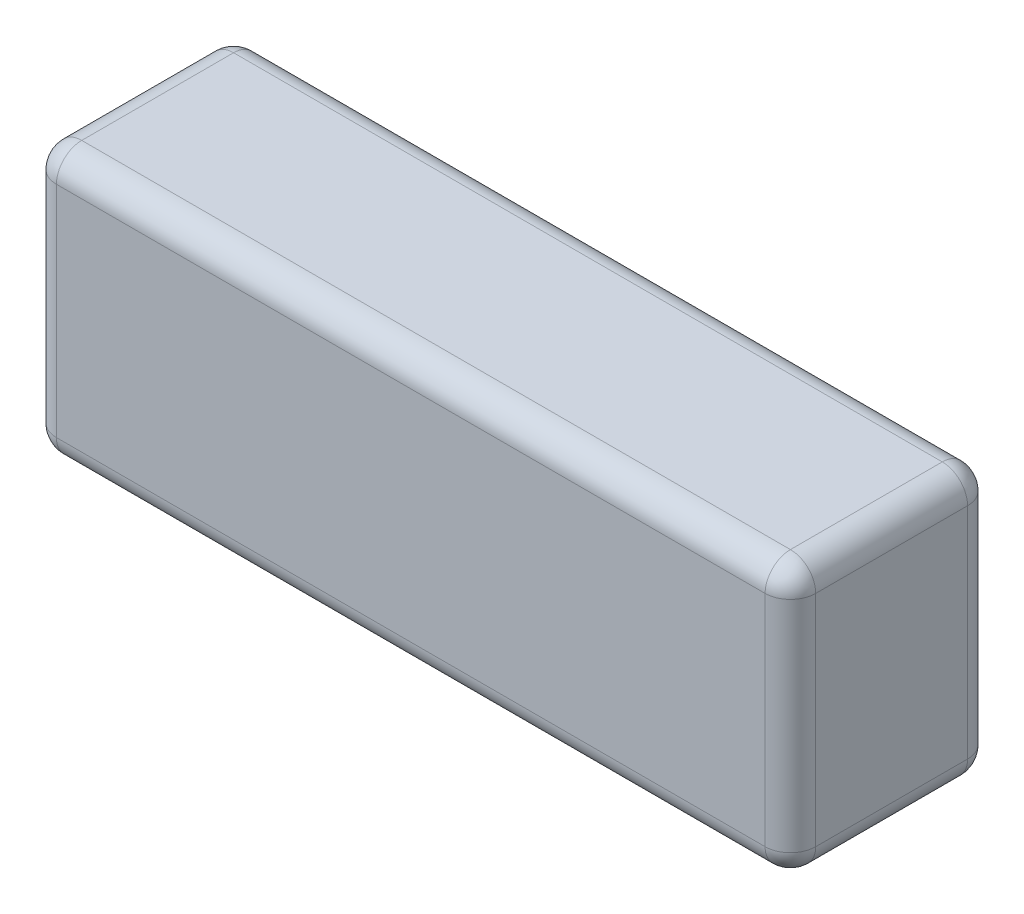
SolidWorks part; units mm, degrees
ref_plane "Plano frontal" through (0, 0, 0) normal (0, 0, 1) x (1, 0, 0)
ref_plane "Plano superior" through (0, 0, 0) normal (0, 1, 0) x (1, 0, 0)
ref_plane "Plano direito" through (0, 0, 0) normal (1, 0, 0) x (0, 0, -1)
sketch "Esboço1" plane through (0, 0, 0) normal (0, 0, 1) x (1, 0, 0)
  line L1 (-19.8795, 12.2892) -> (25.1205, 12.2892)
  line L2 (-19.8795, 12.2892) -> (-19.8795, -3.7108)
  line L3 (-19.8795, -3.7108) -> (25.1205, -3.7108)
  line L4 (25.1205, 12.2892) -> (25.1205, -3.7108)
  dimension "D1" = 45
  dimension "D2" = 16
extrude "Ressalto-extrusão1" add sketch "Esboço1" along normal blind 12
fillet "Filete1" radius 1.5 9 edges at (-19.8795, 4.2892, 0) (2.6205, -3.7108, 0) (25.1205, 4.2892, 0) (2.6205, 12.2892, 0) (-19.8795, 4.2892, 12) (2.6205, -3.7108, 12) (-19.8795, 12.2892, 6) (25.1205, -3.7108, 6) (-19.8795, -3.7108, 6)
fillet "Filete2" radius 1.5 6 edges at (-19.4402, 11.8498, 11.5607) (24.6811, 11.8498, 0.4393) (24.6811, -3.2715, 11.5607) (25.1205, 5.0392, 12) (3.3705, 12.2892, 12) (25.1205, 12.2892, 6.75)
sketch "Esboço2" plane through (0, 0, 0) normal (0, 0, -1) x (-1, 0, 0)
  text T0 "Tattu 2s 300mah"
extrude "Corte-extrusão1" cut sketch "Esboço2" against normal blind 0.1
